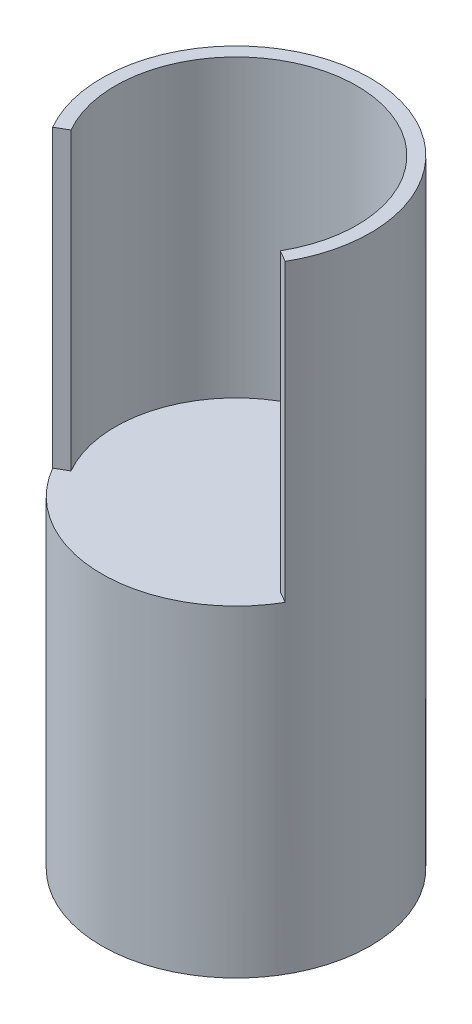
SolidWorks part; units mm, degrees
ref_plane "Front Plane" through (0, 0, 0) normal (0, 0, 1) x (1, 0, 0)
ref_plane "Top Plane" through (0, 0, 0) normal (0, 1, 0) x (1, 0, 0)
ref_plane "Right Plane" through (0, 0, 0) normal (1, 0, 0) x (0, 0, -1)
sketch "Sketch1" plane through (0, 0, 0) normal (0, 1, 0) x (1, 0, 0)
  circle A0 centre (0, 0) radius 63.5
  dimension "D1" = 127
extrude "Boss-Extrude1" add sketch "Sketch1" along normal blind 152.4
sketch "Sketch3" plane through (0, 152.4, 0) normal (0, 1, 0) x (1, 0, 0)
  line L0 (-54.9926, -31.75) -> (-49.4934, -28.575)
  line L1 (49.4934, -28.575) -> (54.9926, -31.75)
  line L2 (0, 0) -> (0, 63.5) construction
  arc A0 (-54.9926, -31.75) -> (54.9926, -31.75) centre (0, 0) cw
  circle A1 centre (0, 0) radius 63.5 construction
  arc A2 (-49.4934, -28.575) -> (49.4934, -28.575) centre (0, 0) cw
  point P6 (48.643, -29.9997)
  point P9 (0, 0)
  point P11 (0, -1.1517)
  dimension "D1" = 57.15
  dimension "D2" = 120
  dimension "D3" = 120
extrude "Boss-Extrude2" add sketch "Sketch3" along normal blind 139.7
